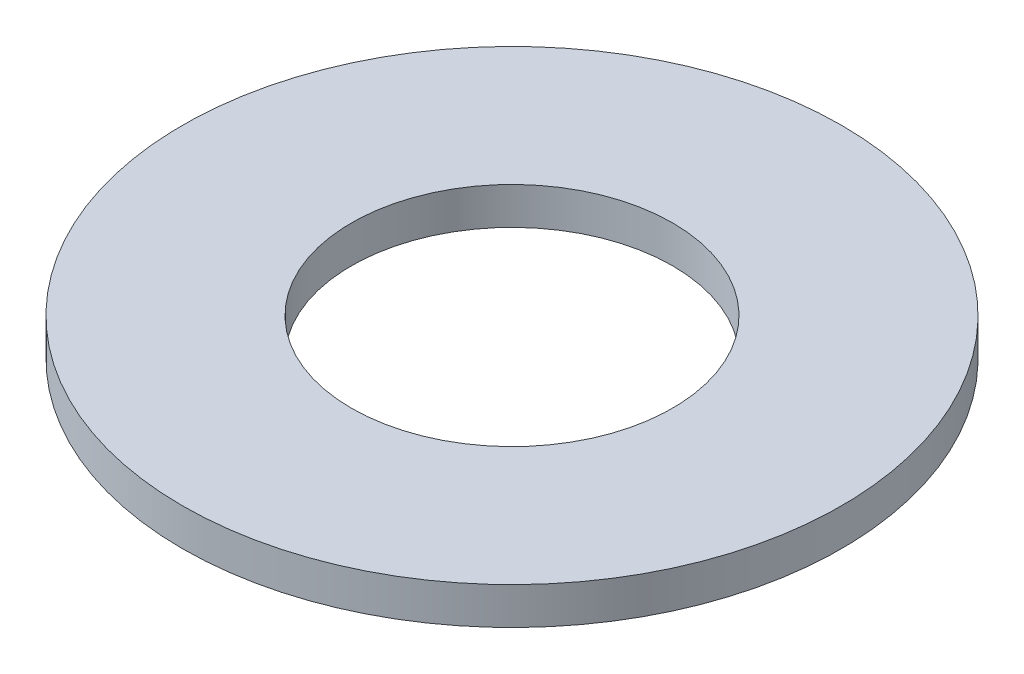
SolidWorks part; units mm, degrees
ref_plane "Front Plane" through (0, 0, 0) normal (0, 0, 1) x (1, 0, 0)
ref_plane "Top Plane" through (0, 0, 0) normal (0, 1, 0) x (1, 0, 0)
ref_plane "Right Plane" through (0, 0, 0) normal (1, 0, 0) x (0, 0, -1)
sketch "Sketch1" plane through (0, 0, 0) normal (0, 1, 0) x (1, 0, 0)
  circle A0 centre (0, 0) radius 97.5
  dimension "FLANGE_OD" = 195
extrude "Boss-Extrude1" add sketch "Sketch1" along normal blind 11
sketch "Sketch2" plane through (0, 0, 0) normal (0, 1, 0) x (1, 0, 0)
  circle A0 centre (0, 0) radius 47.5
  dimension "BORE_D" = 95
extrude "Cut-Extrude1" cut sketch "Sketch2" along normal through all
sketch "Sketch3" plane through (0, 11, 0) normal (0, 1, 0) x (1, 0, 0)
  circle A0 centre (0, 0) radius 36.8246 construction
  circle A1 centre (-36.8246, 0) radius 8.0162
  dimension "BOLT_D" = 16.0324
  dimension "BOLT_PCD" = 73.6492
extrude "Cut-Extrude2" cut sketch "Sketch3" against normal blind 8.9956 rebuild error yes
pattern_circular "CirPattern1" count 4 over 360 rebuild error yes
